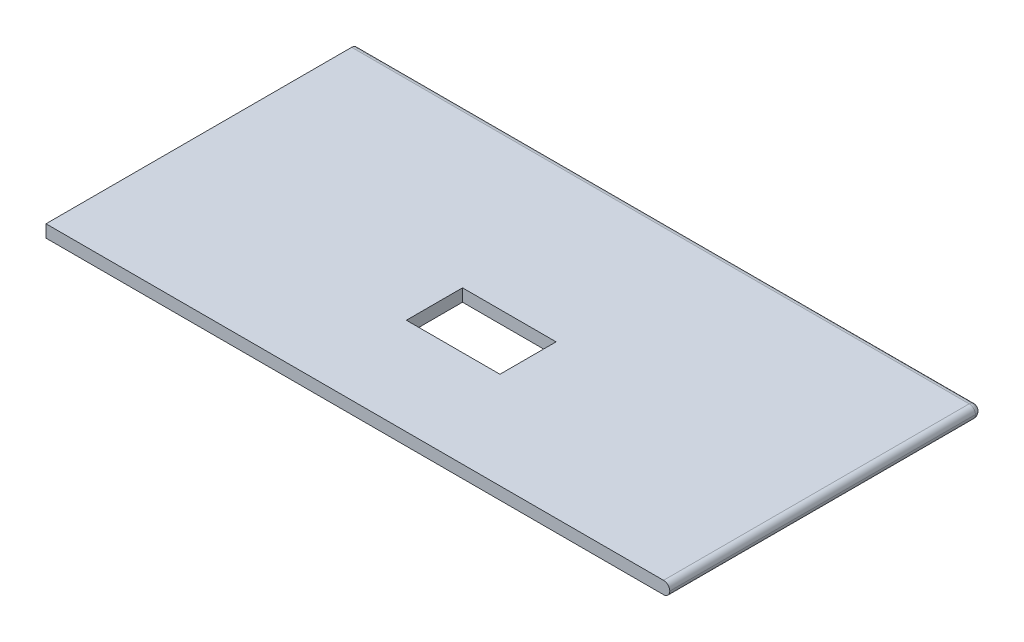
SolidWorks part; units mm, degrees
ref_plane "Piano frontale" through (0, 0, 0) normal (0, 0, 1) x (1, 0, 0)
ref_plane "Piano superiore" through (0, 0, 0) normal (0, 1, 0) x (1, 0, 0)
ref_plane "Piano destro" through (0, 0, 0) normal (1, 0, 0) x (0, 0, -1)
sketch "Schizzo1" plane through (0, 0, 0) normal (0, 1, 0) x (1, 0, 0)
  line L1 (50, -25) -> (-50, -25)
  line L2 (50, -25) -> (50, 25)
  line L3 (50, 25) -> (-50, 25)
  line L4 (-50, -25) -> (-50, 25)
  line L5 (50, -25) -> (-50, 25) construction
  line L6 (50, 25) -> (-50, -25) construction
  point P0 (0, 0)
  dimension "D1" = 100
  dimension "D2" = 50
extrude "Estrusione-Estrusione1" add sketch "Schizzo1" along normal blind 2
fillet "Raccordo1" radius 1 2 edges at (0, 0, -25) (0, 2, -25)
fillet "Raccordo2" radius 1 4 edges at (50, 0.2929, -24.7071) (50, 1.7071, -24.7071) (50, 0, 0.5) (50, 2, 0.5)
sketch "Schizzo2" plane through (0, 2, 0) normal (0, 1, 0) x (1, 0, 0)
  line L2 (-50, -25) -> (49, -25) construction
  line L4 (-7.7209, -0.506) -> (7.2791, -0.506)
  line L5 (-7.7209, -0.506) -> (-7.7209, -9.506)
  line L6 (-7.7209, -9.506) -> (7.2791, -9.506)
  line L7 (7.2791, -0.506) -> (7.2791, -9.506)
  line L8 (-7.7209, -0.506) -> (7.2791, -9.506) construction
  line L9 (-7.7209, -9.506) -> (7.2791, -0.506) construction
  point P0 (0, 0)
  point P1 (0, -9.5)
  point P3 (0, -25)
  point P4 (-0.2209, -5.006)
  point P7 (-0.2209, -5.006)
  dimension "D1" = 9.5
  dimension "D2" = 15.5
  dimension "D3" = 9
  dimension "D4" = 15
extrude "Taglio-Estrusione1" cut sketch "Schizzo2" against normal blind 10
